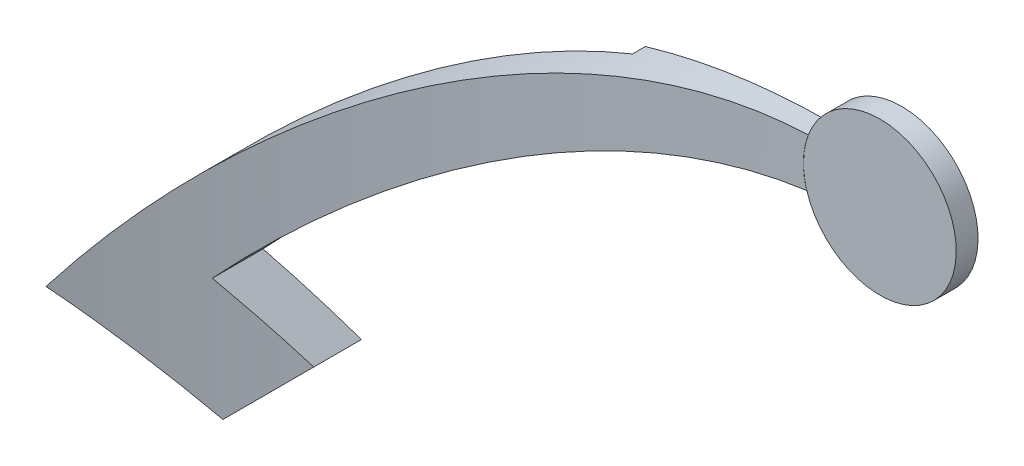
SolidWorks part; units mm, degrees
ref_plane "Front Plane" through (0, 0, 0) normal (0, 0, 1) x (1, 0, 0)
ref_plane "Top Plane" through (0, 0, 0) normal (0, 1, 0) x (1, 0, 0)
ref_plane "Right Plane" through (0, 0, 0) normal (1, 0, 0) x (0, 0, -1)
sketch "Esquisse3" plane through (0, 0, 0) normal (0, 0, 1) x (1, 0, 0)
  line L0 (-56.8066, -24.884) -> (-47.4703, -34.2203)
  line L1 (-47.4703, -34.2203) -> (-42.2091, -28.9591)
  line L2 (-42.2091, -28.9591) -> (-48.0616, -23.1065)
  circle A0 centre (0, 0) radius 7
  arc A1 (-6.5562, 2.4527) -> (-56.8066, -24.884) centre (-6.5355, -57.4388) ccw
  arc A2 (-48.0616, -23.1065) -> (-6.6992, -2.0301) centre (-0.3296, -65.6553) cw
  dimension "D1" = 14
extrude "Boss.-Extru.2" add sketch "Esquisse3" along normal blind 2 contours A0 region at (0, 0, 0)
extrude "Boss.-Extru.3" add sketch "Esquisse3<3>" along normal blind 45 contours L2 A2 A0 A1 L0 L1 region at (-34.8588, -5.3749, 0)
sketch "Esquisse3<3>" plane through (0, 0, 0) normal (0, 0, 1) x (1, 0, 0) same geometry as "Esquisse3"
sketch "Esquisse4" plane through (0, 0, 0) normal (0, 1, 0) x (1, 0, 0)
  line L0 (-6.5562, 0) -> (-6.5562, -2)
  line L4 (-6.5562, -2) -> (-6.5562, 0) construction
  line L6 (-6.5562, -45) -> (-6.5562, -2) construction
  line L8 (-6.5562, -21.6438) -> (-6.5562, -2)
  line L10 (-56.8066, -21.6438) -> (-56.8066, -53.527)
  line L11 (-56.8066, -53.527) -> (-6.4252, -53.527)
  line L12 (-6.4252, -53.527) -> (-6.5562, -21.6438)
  line L13 (-56.8066, -21.6438) -> (-56.8066, -16.6438)
  line L14 (-56.8066, -45) -> (-56.8066, 0) construction
  line L15 (-6.5562, 0) -> (-56.8066, 0) construction
  line L16 (-56.8066, -45) -> (-56.8066, 0)
  line L17 (-6.5562, 0) -> (-56.8066, 0)
  arc A0 (-56.8066, -16.6438) -> (-6.5562, 0) centre (-9.9445, -73.949) cw
  arc A1 (-56.8066, -21.6438) -> (-6.5562, -2) centre (-3.2741, -84.4899) cw
  dimension "D1" = 5
extrude "Enlèv. mat.-Extru.3" cut sketch "Esquisse4" against normal through all and the other way blind 5 contours L8 region at (-29.8785, 0, 30.6926)
extrude "Enlèv. mat.-Extru.4" cut sketch "Esquisse4<4>" against normal through all contours L16 A0 L17 region at (-45.526, 0, 4.8929)
sketch "Esquisse4<4>" plane through (0, 0, 0) normal (0, 1, 0) x (1, 0, 0) same geometry as "Esquisse4"
